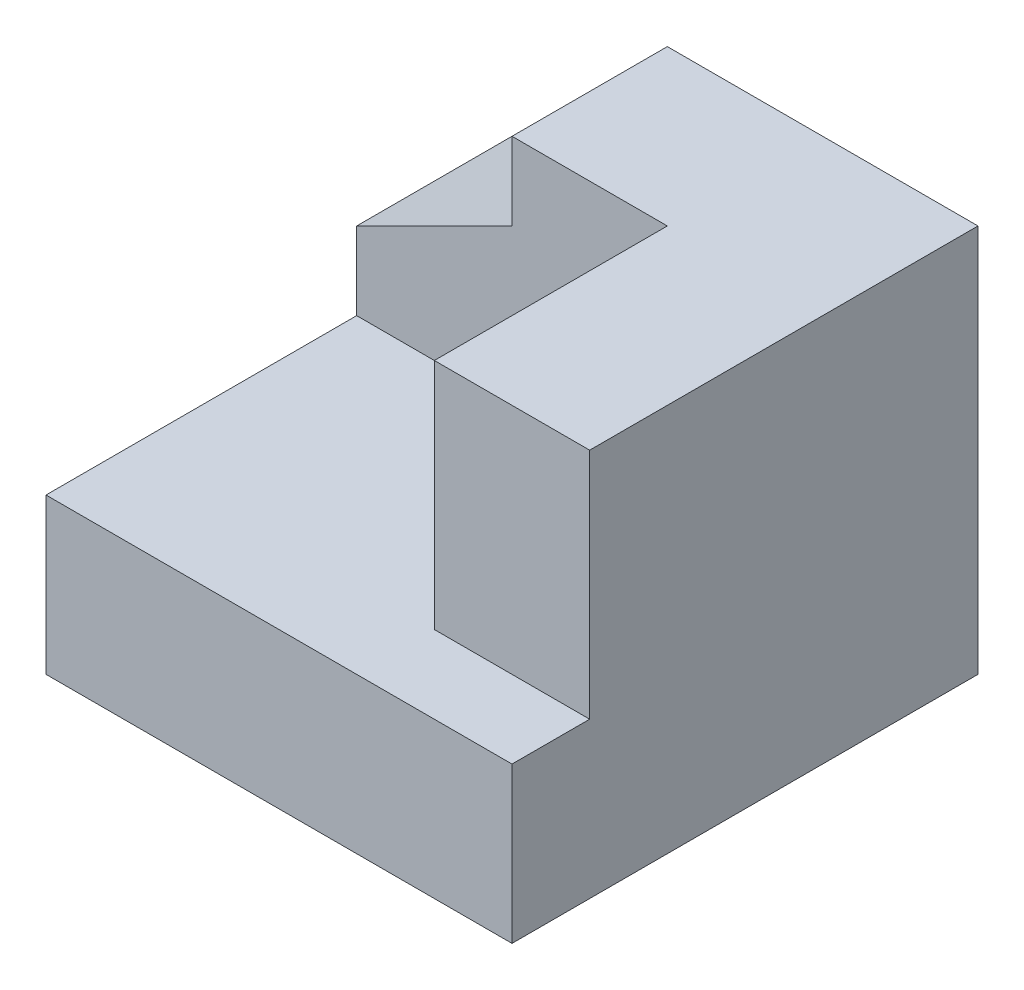
SolidWorks part; units mm, degrees
ref_plane "Front Plane" through (0, 0, 0) normal (0, 0, 1) x (1, 0, 0)
ref_plane "Top Plane" through (0, 0, 0) normal (0, 1, 0) x (1, 0, 0)
ref_plane "Right Plane" through (0, 0, 0) normal (1, 0, 0) x (0, 0, -1)
sketch "Sketch1" plane through (0, 0, 0) normal (0, 0, 1) x (1, 0, 0)
  line L0 (120, -20) -> (-120, -20)
  line L1 (-120, -100) -> (120, -100)
  line L2 (-120, -100) -> (-120, 100)
  line L3 (-120, 100) -> (120, 100)
  line L4 (120, -100) -> (120, 100)
  line L5 (-120, -100) -> (120, 100) construction
  line L6 (-120, 100) -> (120, -100) construction
  line L7 (40, 100) -> (40, -20)
  line L8 (-40, 100) -> (-40, 60)
  line L9 (-40, 60) -> (-120, 20)
  line L10 (-40, 60) -> (-120, 20)
  point P0 (0, 0)
  dimension "D1" = 200
  dimension "D2" = 240
extrude "Boss-Extrude1" add sketch "Sketch1" along normal blind 120 contours L1 L4 L0 L2 region at (0, -60, 0)
extrude "Boss-Extrude2" add sketch "Sketch1<3>" along normal blind 80 contours L3 L7 L0 L4 region at (80, 40, 0)
sketch "Sketch1<3>" plane through (0, 0, 0) normal (0, 0, 1) x (1, 0, 0) same geometry as "Sketch1"
extrude "Boss-Extrude3" add sketch "Sketch1<4>" against normal blind 120 contours L1 L4 L0 L2 region at (0, -60, 0)
sketch "Sketch1<4>" plane through (0, 0, 0) normal (0, 0, 1) x (1, 0, 0) same geometry as "Sketch1"
extrude "Boss-Extrude4" add sketch "Sketch1<5>" against normal blind 120 contours L3 L7 L0 L4 region at (80, 40, 0)
sketch "Sketch1<5>" plane through (0, 0, 0) normal (0, 0, 1) x (1, 0, 0) same geometry as "Sketch1"
sketch "Sketch2" plane through (40, 0, 0) normal (-1, 0, 0) x (0, 0, 1)
  line L0 (-40, 100) -> (-40, -20)
  line L1 (80, 100) -> (-120, 100) construction
  line L2 (80, -20) -> (-120, -20) construction
  line L3 (-40, 60) -> (-120, 60)
  line L4 (-120, 100) -> (-120, -20) construction
  line L5 (-40, 20) -> (-120, 20)
  line M1 (80, 100) -> (-120, 100)
  line M2 (-120, 100) -> (-120, -20)
  line M3 (-120, -20) -> (80, -20)
extrude "Boss-Extrude5" add sketch "Sketch2" along normal blind 160 contours L0 L5 M2 M3 region at (40, 0, -80)
extrude "Boss-Extrude6" add sketch "Sketch2<8>" along normal blind 80 contours L3 L0 M1 M2 region at (40, 80, -80)
sketch "Sketch2<8>" plane through (40, 0, 0) normal (-1, 0, 0) x (0, 0, 1) same geometry as "Sketch2"
extrude "Boss-Extrude7" add sketch "Sketch2<9>" along normal blind 160 contours L5 L0 L3 M2 region at (40, 40, -80)
sketch "Sketch2<9>" plane through (40, 0, 0) normal (-1, 0, 0) x (0, 0, 1) same geometry as "Sketch2"
sketch "Sketch4" plane through (0, 0, -40) normal (0, 0, 1) x (1, 0, 0)
  line L0 (-40, 60) -> (-120, 20)
  line L1 (-120, 60) -> (-120, -20) construction
  line M5 (-40, 60) -> (-120, 60)
  line M6 (-120, 60) -> (-120, -20)
extrude "Cut-Extrude20" cut sketch "Sketch4" against normal blind 121 and the other way through all contours L0 M5 M6 region at (-93.3333, 46.6667, -40)
